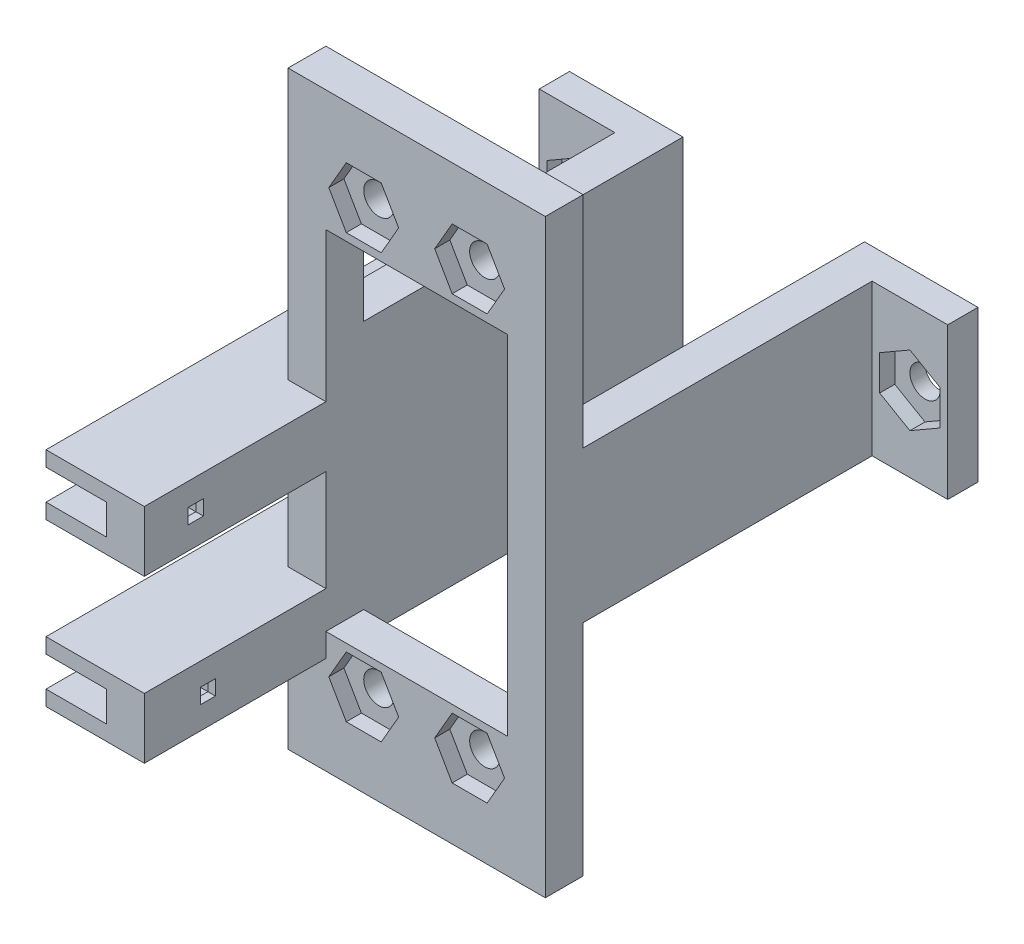
SolidWorks part; units mm, degrees
note: The reader was unsure of these and kept them because the rebuilt part matched: shared geometry of "Sketch1<5>", "Sketch8<3>", "Sketch8<4>".
ref_plane "Front Plane" through (0, 0, 0) normal (0, 0, 1) x (1, 0, 0)
ref_plane "Top Plane" through (0, 0, 0) normal (0, 1, 0) x (1, 0, 0)
ref_plane "Right Plane" through (0, 0, 0) normal (1, 0, 0) x (0, 0, -1)
sketch "Sketch1" plane through (0, 0, 0) normal (0, 0, 1) x (1, 0, 0)
  line L0 (0, 0) -> (0, 19.5) construction
  line L8 (6, 24.5) -> (8.5, 24.5)
  line L9 (-6, 8) -> (6, 8)
  line L10 (-6, 8) -> (-6, 31)
  line L11 (-6, 31) -> (6, 31)
  line L12 (6, 8) -> (6, 31)
  line L13 (0, 31) -> (0, 8) construction
  line L14 (-6, 19.5) -> (6, 19.5) construction
  line L15 (-8.5, 0) -> (8.5, 0)
  line L16 (-8.5, 0) -> (-8.5, 39)
  line L17 (-8.5, 39) -> (8.5, 39)
  line L18 (8.5, 0) -> (8.5, 39)
  line L19 (0, 39) -> (0, 0) construction
  line L20 (-8.5, 19.5) -> (8.5, 19.5) construction
  line L21 (6, 14.5) -> (8.5, 14.5)
  line L22 (-6, 14.5) -> (-8.5, 14.5)
  line L23 (-6, 24.5) -> (-8.5, 24.5)
  circle A0 centre (-3.5, 33.5) radius 1
  circle A1 centre (-3.5, 5.5) radius 1
  circle A2 centre (3.5, 5.5) radius 1
  circle A3 centre (3.5, 33.5) radius 1
  dimension "D9" = 2
  dimension "D2" = 2.5
  dimension "D3" = 12
  dimension "D4" = 23
  dimension "D10" = 28
  dimension "D11" = 14
  dimension "D5" = 10
  dimension "D6" = 3.5
extrude "ServoBracket" add sketch "Sketch1" along normal blind 2.5
extrude "SupportLegs" add sketch "Sketch1<5>" against normal blind 21.1 contours L10 L23 L16 L22 | L12 L21 L18 L8
sketch "Sketch1<5>" plane through (0, 0, 0) normal (0, 0, 1) x (1, 0, 0) same geometry as "Sketch1"
sketch "Sketch2" plane through (-8.5, 0, 0) normal (-1, 0, 0) x (0, 0, 1)
  line L0 (-21.1, 14.5) -> (-21.1, 24.5) construction
  line L1 (-21.1, 14.5) -> (-21.1, 24.5)
  line L2 (-21.1, 14.5) -> (0, 14.5) construction
  line L3 (-21.1, 24.5) -> (0, 24.5) construction
  line L4 (-21.1, 14.5) -> (0, 14.5) construction
  line L5 (-21.1, 24.5) -> (0, 24.5) construction
  line L6 (-19.1, 14.5) -> (-19.1, 24.5)
  line L7 (-21.1, 24.5) -> (-19.1, 24.5)
  line L8 (-21.1, 14.5) -> (-19.1, 14.5)
  dimension "D1" = 2
extrude "SupportFoot" add sketch "Sketch2" along normal blind 5
sketch "Sketch3" plane through (0, 0, -19.1) normal (0, 0, 1) x (1, 0, 0)
  line L0 (-13.5, 19.5) -> (-8.5, 19.5) construction
  line L1 (-13.5, 14.5) -> (-13.5, 24.5) construction
  line L2 (-8.5, 14.5) -> (-8.5, 24.5) construction
  circle A0 centre (-11, 19.5) radius 1
extrude "BaseBoltHole" cut sketch "Sketch3" against normal through all and the other way through all
mirror "SupportFoot2" about plane through (0, 0, 0) normal (1, 0, 0) of "BaseBoltHole", "SupportFoot"
sketch "Sketch4" plane through (0, 0, 2.5) normal (0, 0, 1) x (1, 0, 0)
  line L0 (8.5, 0) -> (8.5, 39) construction
  line L5 (-8.5, 0) -> (-8.5, 39) construction
  line L6 (8.5, 0) -> (8.5, 39) construction
  line L11 (-8.5, 0) -> (-8.5, 39) construction
  line L12 (-8.5, 19.5) -> (8.5, 19.5) construction
  line L21 (0, 19.5) -> (0, 23.2457) construction
  line L22 (-4.6547, 7.5) -> (-2.3453, 7.5)
  line L23 (-1.1906, 33.5) -> (-2.3453, 35.5)
  line L24 (-2.3453, 35.5) -> (-4.6547, 35.5)
  line L25 (-4.6547, 35.5) -> (-5.8094, 33.5)
  line L26 (-5.8094, 33.5) -> (-4.6547, 31.5)
  line L27 (-4.6547, 31.5) -> (-2.3453, 31.5)
  line L28 (-2.3453, 31.5) -> (-1.1906, 33.5)
  line L29 (-5.8094, 5.5) -> (-4.6547, 7.5)
  line L30 (-4.6547, 3.5) -> (-5.8094, 5.5)
  line L31 (-2.3453, 3.5) -> (-4.6547, 3.5)
  line L32 (-1.1906, 5.5) -> (-2.3453, 3.5)
  line L33 (-2.3453, 7.5) -> (-1.1906, 5.5)
  line L34 (2.3453, 31.5) -> (1.1906, 33.5)
  line L35 (1.1906, 33.5) -> (2.3453, 35.5)
  line L36 (2.3453, 35.5) -> (4.6547, 35.5)
  line L37 (4.6547, 35.5) -> (5.8094, 33.5)
  line L38 (5.8094, 33.5) -> (4.6547, 31.5)
  line L39 (4.6547, 31.5) -> (2.3453, 31.5)
  line L40 (4.6547, 7.5) -> (2.3453, 7.5)
  line L41 (5.8094, 5.5) -> (4.6547, 7.5)
  line L42 (4.6547, 3.5) -> (5.8094, 5.5)
  line L43 (2.3453, 3.5) -> (4.6547, 3.5)
  line L44 (1.1906, 5.5) -> (2.3453, 3.5)
  line L45 (2.3453, 7.5) -> (1.1906, 5.5)
  circle A4 centre (-3.5, 33.5) radius 1 construction
  circle A5 centre (-3.5, 33.5) radius 1 construction
  circle A6 centre (-3.5, 33.5) radius 2 construction
  dimension "D1" = 4
extrude "ServoNutSlots" cut sketch "Sketch4" against normal blind 1
sketch "Sketch5" plane through (0, 0, -19.1) normal (0, 0, 1) x (1, 0, 0)
  line L5 (-11, 21.8094) -> (-13, 20.6547)
  line L6 (-13, 20.6547) -> (-13, 18.3453)
  line L11 (-13, 18.3453) -> (-11, 17.1906)
  line L12 (-11, 17.1906) -> (-9, 18.3453)
  line L13 (-9, 18.3453) -> (-9, 20.6547)
  line L14 (-9, 20.6547) -> (-11, 21.8094)
  line L15 (11, 21.8094) -> (9, 20.6547)
  line L16 (9, 20.6547) -> (9, 18.3453)
  line L17 (9, 18.3453) -> (11, 17.1906)
  line L18 (11, 17.1906) -> (13, 18.3453)
  line L19 (13, 18.3453) -> (13, 20.6547)
  line L20 (13, 20.6547) -> (11, 21.8094)
  circle A0 centre (11, 19.5) radius 1 construction
  circle A1 centre (-11, 19.5) radius 1 construction
  circle A2 centre (11, 19.5) radius 1 construction
  circle A3 centre (-11, 19.5) radius 1 construction
  circle A4 centre (-11, 19.5) radius 2 construction
  circle A5 centre (11, 19.5) radius 2 construction
  dimension "D1" = 4
  dimension "D2" = 4
extrude "BaseNutSlots" cut sketch "Sketch5" against normal blind 1
sketch "Sketch6" plane through (0, 0, 2.5) normal (0, 0, 1) x (1, 0, 0)
  line L0 (0, 8) -> (0, 13.8) construction
  line L1 (-6, 8) -> (6, 8) construction
  line L3 (-6, 8) -> (-6, 31) construction
  line L4 (0, 18.8) -> (0, 19.5) construction
  line L5 (-7.5, 13.8) -> (-8.2, 13.8) construction
  line L10 (-7.25, 19.15) -> (0, 19.15) construction
  line L11 (-8.5, 17.15) -> (-6, 17.15)
  line L12 (-8.5, 17.15) -> (-8.5, 21.15)
  line L27 (-8.5, 21.15) -> (-6, 21.15)
  line L28 (-6, 17.15) -> (-6, 21.15)
  line L31 (-7.25, 21.15) -> (-7.25, 17.15) construction
  line L32 (-8.5, 19.15) -> (-6, 19.15) construction
  circle A2 centre (3.5, 5.5) radius 1 construction
  circle A3 centre (3.5, 5.5) radius 1 construction
  circle A4 centre (0, 13.8) radius 5 construction
  circle A5 centre (0, 13.8) radius 5.7 construction
  dimension "D6" = 10
  dimension "D1" = 8.3
  dimension "D7" = 0.7
  dimension "D4" = 4
  dimension "D5" = 2.5
extrude "TubeHolderBase" add sketch "Sketch6" along normal blind 12
sketch "Sketch7" plane through (0, 0, 14.5) normal (0, 0, 1) x (1, 0, 0)
  line L0 (-8.5, 19.15) -> (-10.929, 19.15) construction
  line L1 (-8.5, 21.15) -> (-12.5, 21.15)
  line L2 (-8.5, 21.15) -> (-8.5, 20.15)
  line L3 (-8.5, 20.15) -> (-12.5, 20.15)
  line L4 (-12.5, 21.15) -> (-12.5, 20.15)
  line L5 (-8.5, 21.15) -> (-8.5, 17.15) construction
  line L6 (-8.5, 17.15) -> (-8.5, 18.15)
  line L7 (-8.5, 17.15) -> (-12.5, 17.15)
  line L8 (-12.5, 17.15) -> (-12.5, 18.15)
  line L9 (-8.5, 18.15) -> (-12.5, 18.15)
  dimension "D1" = 4
  dimension "D2" = 1
extrude "TubeHolderStiffenerRibs" add sketch "Sketch7" against normal offset from surface (30.6 mm away) 3 up to face at (-11, 19.5, -19.1)
ref_plane "Plane1" through (0, 5.5, 0) normal (0, 1, 0) x (1, 0, 0)
ref_plane "Plane2" through (0, 13.8, 0) normal (0, 1, 0) x (1, 0, 0)
mirror "TubeHolder2" about plane through (0, 13.8, 0) normal (0, 1, 0) of "TubeHolderBase", "TubeHolderStiffenerRibs"
sketch "Sketch8" plane through (-8.5, 0, 0) normal (-1, 0, 0) x (0, 0, 1)
  line L0 (2.5, 21.15) -> (2.5, 39) construction
  line L1 (2.5, 21.15) -> (2.5, 39) construction
  line L2 (0, 7.45) -> (14.5, 7.45) construction
  line L3 (0, 9.45) -> (14.5, 9.45) construction
  line L4 (-16.1, 18.15) -> (14.5, 18.15) construction
  line L5 (-16.1, 20.15) -> (14.5, 20.15) construction
  line L6 (0, 7.45) -> (14.5, 7.45) construction
  line L7 (0, 9.45) -> (14.5, 9.45) construction
  line L8 (-16.1, 18.15) -> (14.5, 18.15) construction
  line L9 (-16.1, 20.15) -> (14.5, 20.15) construction
  line L10 (11.1, 20.15) -> (11.1, 18.15) construction
  line L11 (10.3, 9.45) -> (10.3, 7.45) construction
  line L12 (11.85, 19.9) -> (12.05, 19.9)
  line L13 (9.8, 7.95) -> (10.8, 7.95)
  line L14 (9.8, 7.95) -> (9.8, 8.95)
  line L15 (9.8, 8.95) -> (10.8, 8.95)
  line L16 (10.8, 7.95) -> (10.8, 8.95)
  line L17 (10.3, 8.95) -> (10.3, 7.95) construction
  line L18 (9.8, 8.45) -> (10.8, 8.45) construction
  line L19 (9.55, 7.7) -> (11.05, 7.7)
  line L20 (9.55, 7.7) -> (9.55, 9.2)
  line L21 (9.55, 9.2) -> (11.05, 9.2)
  line L22 (11.05, 7.7) -> (11.05, 9.2)
  line L23 (10.3, 9.2) -> (10.3, 7.7) construction
  line L24 (9.55, 8.45) -> (11.05, 8.45) construction
  line L25 (12.05, 19.9) -> (12.05, 18.4)
  line L26 (10.6, 18.65) -> (11.6, 18.65)
  line L27 (10.6, 18.65) -> (10.6, 19.65)
  line L28 (10.6, 19.65) -> (11.6, 19.65)
  line L29 (11.6, 18.65) -> (11.6, 19.65)
  line L30 (11.1, 19.65) -> (11.1, 18.65) construction
  line L31 (10.6, 19.15) -> (11.6, 19.15) construction
  line L32 (10.35, 18.4) -> (11.85, 18.4)
  line L33 (10.35, 18.4) -> (10.35, 19.9)
  line L34 (10.35, 19.9) -> (11.85, 19.9)
  line L35 (11.85, 18.4) -> (11.85, 19.9)
  line L36 (11.1, 19.9) -> (11.1, 18.4) construction
  line L37 (10.35, 19.15) -> (11.85, 19.15) construction
  line L38 (12.05, 18.4) -> (11.85, 18.4)
  line L39 (11.05, 9.2) -> (11.25, 9.2)
  line L40 (11.25, 9.2) -> (11.25, 7.7)
  line L41 (11.25, 7.7) -> (11.05, 7.7)
  point P14 (10.3, 8.45)
  point P18 (10.3, 8.45)
  point P22 (11.1, 19.15)
  point P24 (11.1, 19.15)
  dimension "D1" = 8.6
  dimension "D2" = 7.8
  dimension "D4" = 1.5
  dimension "D5" = 1.5
  dimension "D7" = 1.5
  dimension "D8" = 1.5
  dimension "D10" = 0.2
extrude "TubeClipEntrances" cut sketch "Sketch8" against normal offset from surface (2 mm away) 0.5 contours L26 L29 L28 L27 | L32 L35 L34 L33 L29 L26 L27 L28 | L13 L16 L15 L14 | L19 L22 L21 L20 L16 L13 L14 L15 up to face at (-6, 16.65, 1.925)
extrude "CableExits" cut sketch "Sketch8<3>" against normal up to surface (2.5 mm away) contours L26 L29 L28 L27 | L13 L16 L15 L14 up to face at (-6, 16.65, 1.925)
sketch "Sketch8<3>" plane through (-8.5, 0, 0) normal (-1, 0, 0) x (0, 0, 1) same geometry as "Sketch8"
sketch "Sketch9" plane through (0, 0, 11.85) normal (0, 0, -1) x (-1, 0, 0)
  line L0 (8, 19.9) -> (8, 18.4)
  line L4 (6.5, 19.9) -> (6.5, 18.4)
  line L5 (6.5, 18.4) -> (8.5, 18.4)
  line L6 (8.5, 18.4) -> (8.5, 19.9)
  line L7 (8.5, 19.9) -> (6.5, 19.9)
  line L8 (6.5, 19.9) -> (6.5, 18.4)
  line L9 (6.5, 18.4) -> (8.5, 18.4)
  line L10 (8.5, 18.4) -> (8.5, 19.9)
  line L11 (8.5, 19.9) -> (6.5, 19.9)
  line M6 (6.5, 19.9) -> (6.5, 18.4)
  line M7 (6.5, 18.4) -> (8.5, 18.4)
  line M9 (8.5, 19.9) -> (6.5, 19.9)
  dimension "D2" = 0.5
  dimension "D1" = 0
extrude "TubeClipLockSlot" cut sketch "Sketch9" against normal blind 0.6 contours L0 M9 M6 M7
sketch "Sketch10" plane through (0, 0, 11.05) normal (0, 0, -1) x (-1, 0, 0)
  line L0 (8, 9.2) -> (8, 7.7)
  line L4 (6.5, 9.2) -> (6.5, 7.7)
  line L5 (6.5, 7.7) -> (8.5, 7.7)
  line L6 (8.5, 7.7) -> (8.5, 9.2)
  line L7 (8.5, 9.2) -> (6.5, 9.2)
  line L8 (6.5, 9.2) -> (6.5, 7.7)
  line L9 (6.5, 7.7) -> (8.5, 7.7)
  line L10 (8.5, 7.7) -> (8.5, 9.2)
  line L11 (8.5, 9.2) -> (6.5, 9.2)
  line M6 (6.5, 9.2) -> (6.5, 7.7)
  line M7 (6.5, 7.7) -> (8.5, 7.7)
  line M9 (8.5, 9.2) -> (6.5, 9.2)
  dimension "D2" = 0.5
  dimension "D1" = 0
extrude "TubeClipLockSlot2" cut sketch "Sketch10" against normal blind 0.6 contours L0 M9 M6 M7
sketch "Sketch11" plane through (0, 14.5, 0) normal (0, -1, 0) x (1, 0, 0)
  line L6 (-6, 0) -> (-8.5, 0)
  line L7 (-8.5, 0) -> (-8.5, -19.1)
  line L8 (-8.5, -19.1) -> (-13.5, -19.1)
  line L9 (-13.5, -19.1) -> (-13.5, -21.1)
  line L10 (-13.5, -21.1) -> (-6, -21.1)
  line L11 (-6, -21.1) -> (-6, 0)
  line L12 (-6, 0) -> (-8.5, 0)
  line L13 (-8.5, 0) -> (-8.5, -19.1)
  line L14 (-8.5, -19.1) -> (-13.5, -19.1)
  line L15 (-13.5, -19.1) -> (-13.5, -21.1)
  line L16 (-13.5, -21.1) -> (-6, -21.1)
  line L17 (-6, -21.1) -> (-6, 0)
  dimension "D1" = 0
extrude "SupportLegExtension" add sketch "Sketch11" along normal up to surface (8.05 mm away)
extrude "TubeClipLockClearance" cut sketch "Sketch8<4>" against normal blind 0.5 contours L41 L40 L39 L22 | L38 L25 L12 L35
sketch "Sketch8<4>" plane through (-8.5, 0, 0) normal (-1, 0, 0) x (0, 0, 1) same geometry as "Sketch8"
equation "\"D8@Sketch1\"=\"BoltD\""
equation "\"D9@Sketch1\"=\"BoltD\""
equation "\"BoltD\"=2mm"
equation "\"NutShortSide\"=4mm"
equation "\"NutLongSide\"=4.5mm"
equation "\"D3@Sketch1\"=\"KST_ServoWidth\""
equation "\"D11@Sketch1\" = \"KST_ServoBoltHole2HoleLength\" / 2"
equation "\"D10@Sketch1\" = \"KST_ServoBoltHole2HoleLength\""
equation "\"D4@Sketch1\" = \"KST_ServoLength\""
equation "\"D1@Sketch3\"=\"BoltD\""
equation "\"BasicPulleyD\"=15mm"
equation "\"GrooveDepth\"=0.7mm"
equation "\"SmallScrewD\"=1.2mm"
equation "\"TubeOuterD\"=1.2mm"
equation "\"BoltHatD\"=3.2mm"
equation "\"SmallScrewHatD\"=2mm"
equation "\"Cable1D\"=0.4mm"
equation "\"Cable2D\"=0.3mm"
equation "\"BallBearingInnerD\"=2mm"
equation "\"BallBearingOuterD\"=4mm"
equation "\"BallBearingThickness\"=2mm"
equation "\"HumerusL\"=37.2mm"
equation "\"HumerusElbowSidePulleyD\"=10mm"
equation "\"RadiusL\"=68.1mm"
equation "\"Finger1L\"=120mm"
equation "\"Finger2L\"=100mm"
equation "\"Finger3L\"=80mm"
equation "\"ElbowExtendedAngle\"=140deg"
equation "\"ElbowFlexedAngle\"=38deg"
equation "\"D1@SupportLegs\"=\"KST_ServoBoltShelfHeight\""
equation "\"BearingCapD\"=12mm"
equation "\"TubeClipW\"=1.5mm"
equation "\"TubeClipH\"=1.5mm"
equation "\"TubeClipLock_SideL\"=1.5mm"
equation "\"TubeClipLock_W\"=0.7mm"
equation "\"Digit5ExtendedAngle\"=80deg"
equation "\"Digit5FlexedAngle\"=24deg"
equation "\"Digit4ExtendedAngle\"=108deg"
equation "\"Digit4FlexedAngle\"=34deg"
equation "\"Digit3ExtendedAngle\"=145deg"
equation "\"Digit3FlexedAngle\"=44deg"
equation "\"KST_ServoBoltShelfHeight\"=21.1mm"
equation "\"KST_ServoLength\"=23mm"
equation "\"KST_ServoWidth\"=12mm"
equation "\"KST_ServoBoltHole2HoleLength\"=28mm"
equation "\"KST_ServoBoltHole2ShaftDist\"=8.3mm"
equation "\"KST_ServoBoltHole2HoleWidth\"=7mm"
equation "\"KST_ServoHeight\"=27.5mm"
equation "\"KST_ServoShaftHeight\"=3.5mm"
equation "\"KST_ServoShaftD\"=4.25mm"
equation "\"KST_ServoShaftToothL\"=0.345mm"
equation "\"D6@Sketch1\"=\"KST_ServoBoltHole2HoleWidth\"/2"
equation "\"D1@Sketch6\"=\"KST_ServoBoltHole2ShaftDist\""
equation "\"D1@Plane2\"=\"KST_ServoBoltHole2ShaftDist\""
equation "\"D6@Sketch6\"  = \"HumerusElbowSidePulleyD\""
equation "\"D7@Sketch6\"=\"GrooveDepth\""
equation "\"KST_ServoShaftToothAngle\"=60deg"
equation "\"KST_ServoShaftToothTipWidth\"=0.18mm"
equation "\"KST_ServoShaftToothFilletR\"=0.1mm"
equation "\"KST_ServoShaftToothN\"=25"
equation "\"KST_ServoShaftBoltD\"=2mm"
equation "\"KST_ServoShaftBoltHatD\"=5mm"
equation "\"XL330_M077_T_Length\"=34mm"
equation "\"XL330_M077_T_Width\"=20mm"
equation "\"XL330_M077_T_Height\"=23mm"
equation "\"XL330_M077_T_BoltHole2HoleLength\"=30mm"
equation "\"XL330_M077_T_BoltHole2HoleWidth\"=16mm"
equation "\"XL330_M077_T_BoltHole2ShaftDist\"=7.5mm"
equation "\"XL330_M077_T_HornHeight\"=3mm"
equation "\"XL330_M077_T_HornBoltD\"=2mm"
equation "\"XL330_M077_T_HornBoltHatD\"=5.6mm"
equation "\"XL330_M077_T_HornScrewHoleCircleD\"=12mm"
equation "\"XL330_M077_T_FrameBoltD\"=1.6mm"
equation "\"XL330_M077_T_FrameNutShortSide\"=2.5mm"
equation "\"XL330_M077_T_FrameNutLongSide\"=3mm"
equation "\"XL330_M077_T_HornD\"=16mm"
equation "\"XL330_M077_T_BoltD\"=1.6mm"
equation "\"D1@Sketch4\"=\"NutShortSide\""
equation "\"D2@Sketch5\"=\"NutShortSide\""
equation "\"D4@Sketch8\"=\"TubeClipW\""
equation "\"D5@Sketch8\"=\"TubeClipH\""
equation "\"D7@Sketch8\"=\"TubeClipW\""
equation "\"D8@Sketch8\"=\"TubeClipH\""
